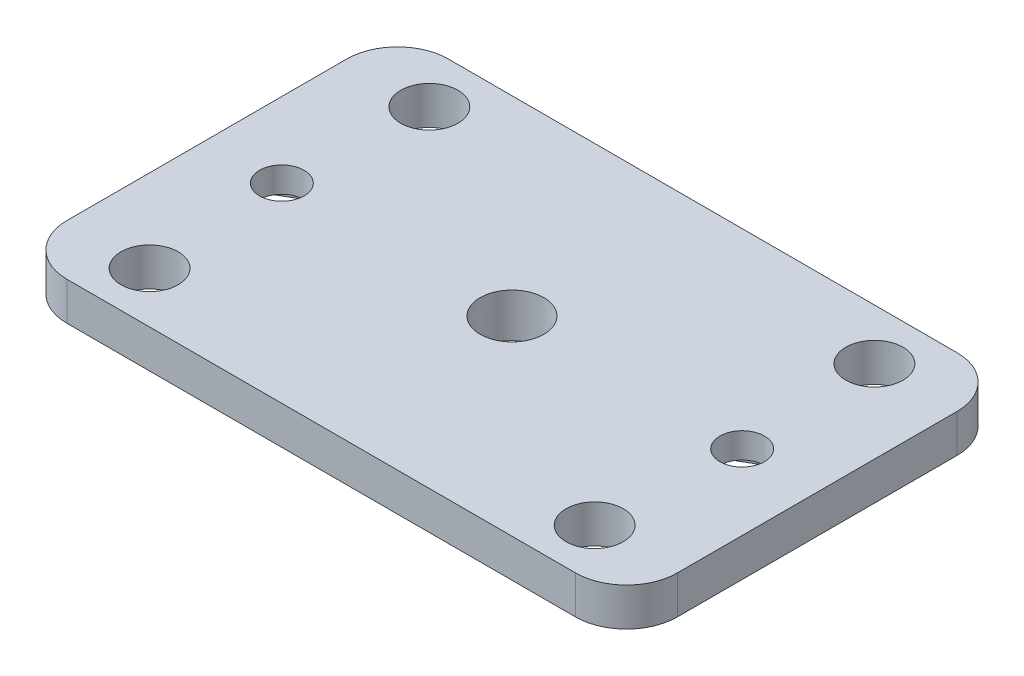
SolidWorks part; units mm, degrees
ref_plane "Plano frontal" through (0, 0, 0) normal (0, 0, 1) x (1, 0, 0)
ref_plane "Plano superior" through (0, 0, 0) normal (0, 1, 0) x (1, 0, 0)
ref_plane "Plano direito" through (0, 0, 0) normal (1, 0, 0) x (0, 0, -1)
sketch "Esboço1" plane through (0, 0, 0) normal (0, 1, 0) x (1, 0, 0)
  line L1 (21, -1.6743) -> (18.1, -3.3486)
  line L3 (0, 15.7272) -> (0, 10.75) construction
  line L4 (-18.1, -3.3486) -> (-15.2, -1.6743)
  line L5 (-15.2, -1.6743) -> (-15.2, 1.6743)
  line L6 (-15.2, 1.6743) -> (-18.1, 3.3486)
  line L7 (-18.1, 3.3486) -> (-21, 1.6743)
  line L8 (0, 10.75) -> (0, 0) construction
  line L14 (-19.5991, -11.8101) -> (-22.8284, -13.8284) construction
  line L15 (-20, -15) -> (20, -15)
  line L16 (-24, -11) -> (-24, 11)
  line L17 (-20, 15) -> (20, 15)
  line L18 (24, -11) -> (24, 11)
  line L19 (-24, -15) -> (24, 15) construction
  line L20 (-24, 15) -> (24, -15) construction
  line L21 (-17.5, -11) -> (17.5, -11) construction
  line L22 (17.5, -11) -> (17.5, 11) construction
  line L23 (17.5, 11) -> (-17.5, 11) construction
  line L24 (-17.5, 11) -> (-17.5, -11) construction
  line L25 (17.5, 0) -> (-17.5, 0) construction
  line L26 (-21, 1.6743) -> (-21, -1.6743)
  line L27 (-21, -1.6743) -> (-18.1, -3.3486)
  line L28 (21, 1.6743) -> (21, -1.6743)
  line L29 (18.1, 3.3486) -> (21, 1.6743)
  line L30 (15.2, 1.6743) -> (18.1, 3.3486)
  line L31 (15.2, -1.6743) -> (15.2, 1.6743)
  line L32 (18.1, -3.3486) -> (15.2, -1.6743)
  line L33 (-17.5, 0) -> (-18.1, 0) construction
  circle A0 centre (0, 0) radius 2.5023
  circle A1 centre (0, 0) radius 12.0853
  circle A2 centre (0, 0) radius 12.6381
  circle A3 centre (0, 0) radius 13.75
  circle A4 centre (-18.1, 0) radius 2.9 construction
  circle A5 centre (0, 0) radius 3.5
  arc A6 (-20, -15) -> (-24, -11) centre (-20, -11) cw
  arc A7 (20, -15) -> (24, -11) centre (20, -11) ccw
  arc A8 (20, 15) -> (24, 11) centre (20, 11) cw
  arc A9 (-24, 11) -> (-20, 15) centre (-20, 11) cw
  circle A10 centre (-17.5, -11) radius 2.25
  circle A11 centre (-17.5, 11) radius 2.25
  circle A12 centre (17.5, -11) radius 2.25
  circle A13 centre (17.5, 11) radius 2.25
  circle A14 centre (-18.1, 0) radius 1.75
  circle A15 centre (18.1, 0) radius 1.75
  point P23 (0, 0)
  point P52 (0, 0)
  point P57 (0, 11)
  point P59 (17.5, 0)
  dimension "D1" = 5.0045
  dimension "D2" = 0.5528
  dimension "D3" = 1.1119
  dimension "D4" = 27.5
  dimension "D6" = 5.8
  dimension "D10" = 4
  dimension "D12" = 4.5
  dimension "D14" = 7
  dimension "D5" = 22
  dimension "D15" = 3.5
  dimension "D7" = 3
  dimension "D8" = 48
  dimension "D9" = 30
  dimension "D11" = 22
  dimension "D13" = 35
extrude "Ressalto-extrusão1" add sketch "Esboço1" along normal blind 3 contours A9 L16 A6 L15 A7 L18 A8 L17 A13 A12 A11 A10 A3 | A3 A2 | A2 A1 | A1 A5 | L26 L27 L4 L5 L6 L7 | L32 L1 L28 L29 L30 L31 | A5 A0 region at (19.5057, 0, 2.4347) region at (-19.5057, 0, 2.4347) region at (-22.4282, 0, 13.4282) region at (-11.7434, 0, 0) region at (-12.2806, 0, 0) region at (-13.3611, 0, 0) region at (-3.401, 0, 0)
extrude "Corte-extrusão1" cut sketch "Esboço1<3>" along normal offset from surface (1 mm away) 2 contours L26 L27 L4 L5 L6 L7 | L32 L1 L28 L29 L30 L31 region at (19.5057, 0, 2.4347) region at (-19.5057, 0, 2.4347) up to face at (17.5, 3, -8.75)
sketch "Esboço1<3>" plane through (0, 0, 0) normal (0, 1, 0) x (1, 0, 0) same geometry as "Esboço1"
extrude "Corte-extrusão3" cut sketch "Esboço1<4>" along normal blind 0.55 contours A3
sketch "Esboço1<4>" plane through (0, 0, 0) normal (0, 1, 0) x (1, 0, 0) same geometry as "Esboço1"
sketch "Esboço2" plane through (0, 0.55, 0) normal (0, -1, 0) x (1, 0, 0)
  circle A0 centre (0, 0) radius 3.5023
  circle A1 centre (0, 0) radius 2.5023 construction
  circle A2 centre (0, 0) radius 2.5023
  dimension "D1" = 1
extrude "Ressalto-extrusão2" add sketch "Esboço2" along normal blind 1
extrude "Corte-extrusão4" cut sketch "Esboço1<5>" along normal blind 1.45 contours A1 A5 region at (-11.7434, 0, 0)
sketch "Esboço1<5>" plane through (0, 0, 0) normal (0, 1, 0) x (1, 0, 0) same geometry as "Esboço1"
sketch "Esboço3" plane through (0, 3, 0) normal (0, 1, 0) x (1, 0, 0)
  line L4 (-24, 11) -> (-24, -11)
  line L5 (-20, -15) -> (20, -15)
  line L6 (24, -11) -> (24, 11)
  line L7 (20, 15) -> (-20, 15)
  line L8 (-24, 11) -> (-24, -11)
  line L9 (-20, -15) -> (20, -15)
  line L10 (24, -11) -> (24, 11)
  line L11 (20, 15) -> (-20, 15)
  arc A4 (-20, 15) -> (-24, 11) centre (-20, 11) ccw
  arc A5 (-24, -11) -> (-20, -15) centre (-20, -11) ccw
  arc A6 (20, -15) -> (24, -11) centre (20, -11) ccw
  arc A7 (24, 11) -> (20, 15) centre (20, 11) ccw
  arc A8 (-20, 15) -> (-24, 11) centre (-20, 11) ccw
  arc A9 (-24, -11) -> (-20, -15) centre (-20, -11) ccw
  arc A10 (20, -15) -> (24, -11) centre (20, -11) ccw
  arc A11 (24, 11) -> (20, 15) centre (20, 11) ccw
  dimension "D1" = 0
